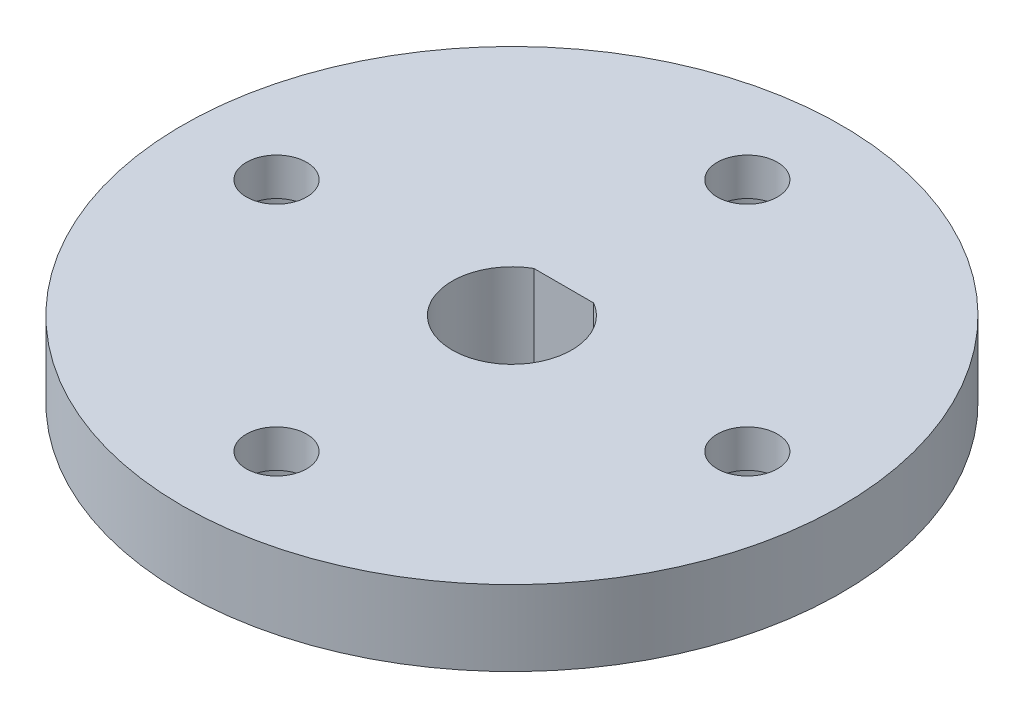
SolidWorks part; units mm, degrees
ref_plane "Front Plane" through (0, 0, 0) normal (0, 0, 1) x (1, 0, 0)
ref_plane "Top Plane" through (0, 0, 0) normal (0, 1, 0) x (1, 0, 0)
ref_plane "Right Plane" through (0, 0, 0) normal (1, 0, 0) x (0, 0, -1)
sketch "Sketch1" plane through (0, 0, 0) normal (0, 1, 0) x (1, 0, 0)
  circle A0 centre (0, 0) radius 17.5
  dimension "D1" = 35
extrude "Boss-Extrude1" add sketch "Sketch1" along normal blind 4
sketch "Sketch2" plane through (0, 0, 0) normal (0, 1, 0) x (1, 0, 0)
  line L0 (-2.87, 6.9291) -> (2.87, 6.9291)
  arc A0 (-2.87, 6.9291) -> (2.87, 6.9291) centre (0, 0) ccw
  dimension "D1" = 15
  dimension "D2" = 5.74
extrude "Boss-Extrude2" add sketch "Sketch2" against normal blind 6
sketch "Sketch3" plane through (0, 0, 0) normal (0, 1, 0) x (1, 0, 0)
  line L0 (0, -14.0033) -> (0, 14.0033) construction
  line L1 (-17.3956, 0) -> (17.3956, 0) construction
  line L2 (-1.5875, 2.7496) -> (1.5875, 2.7496)
  circle A0 centre (0, 0) radius 12.5 construction
  circle A1 centre (0, 12.5) radius 1.6
  circle A2 centre (12.5, 0) radius 1.6
  circle A3 centre (0, -12.5) radius 1.6
  circle A4 centre (-12.5, 0) radius 1.6
  arc A5 (-1.5875, 2.7496) -> (1.5875, 2.7496) centre (0, 0) ccw
  point P6 (0, 0)
  point P8 (0, 0)
  dimension "D1" = 25
  dimension "D2" = 3.2
  dimension "D3" = 6.35
  dimension "D4" = 3.175
extrude "Cut-Extrude1" cut sketch "Sketch3" against normal through all both and the other way through all
sketch "Sketch5" plane through (0, 0, 0) normal (0, 0, 1) x (1, 0, 0)
  line L0 (2.87, -6) -> (-2.87, -6) construction
  circle A0 centre (0, -3) radius 2.1
  dimension "D1" = 4.2
  dimension "D2" = 3
extrude "Cut-Extrude2" cut sketch "Sketch5" against normal through all and the other way blind 1 from surface starting at face at (0, -1, -2.7496)
chamfer "Chamfer1" distance 0.5 angle 45 1 edges at (-2.1, -3, -6.9291)
sketch "Sketch6" plane through (0, 0, 0) normal (0, 1, 0) x (1, 0, 0)
  circle A0 centre (0, 12.5) radius 3
  circle A1 centre (12.5, 0) radius 3
  circle A2 centre (0, -12.5) radius 3
  circle A3 centre (-12.5, 0) radius 3
  dimension "D1" = 6
extrude "Cut-Extrude3" cut sketch "Sketch6" along normal blind 2 from surface starting at face at (0, 0, -10.9)
